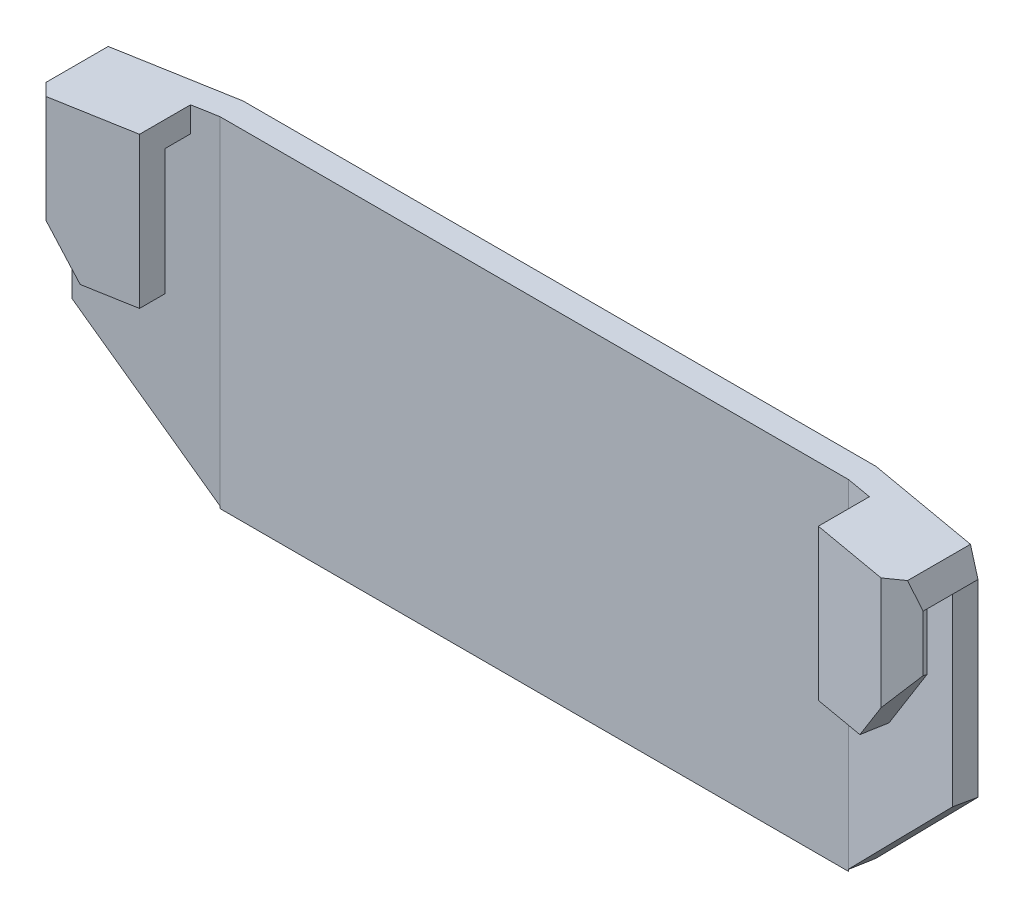
SolidWorks part; units mm, degrees
ref_plane "Front Plane" through (0, 0, 0) normal (0, 0, 1) x (1, 0, 0)
ref_plane "Top Plane" through (0, 0, 0) normal (0, 1, 0) x (1, 0, 0)
ref_plane "Right Plane" through (0, 0, 0) normal (1, 0, 0) x (0, 0, -1)
sketch "Sketch12" plane through (0, 0, 0) normal (0, 1, 0) x (1, 0, 0)
  line L24 (-27, -6.4144) -> (-27, -2.3527)
  line L25 (-27, -2.3527) -> (-25, -2)
  line L26 (35.0231, -1.7365) -> (25.175, 0)
  line L27 (25.175, 0) -> (-25.175, 0)
  line L28 (-25.175, 0) -> (-35.0231, -1.7365)
  line L29 (-25, -2) -> (25, -2)
  line L30 (35.0231, -7.829) -> (27, -6.4144)
  line L31 (27, -6.4144) -> (27, -2.3527)
  line L32 (-35.0231, -7.829) -> (-27, -6.4144)
  line L33 (-35.0231, -1.7365) -> (-35.0231, -7.829)
  line L34 (35.0231, -1.7365) -> (35.0231, -7.829)
  line L35 (27, -2.3527) -> (25, -2)
  point P12 (0, 0)
  dimension "D1" = 25
  dimension "D2" = 25.175
  dimension "D3" = 27
  dimension "D4" = 35.0231
  dimension "D5" = 1.7365
  dimension "D6" = 2
  dimension "D7" = 6.4144
extrude "Boss-Extrude1" add sketch "Sketch12" along normal blind 2
sketch "Sketch13" plane through (0, 0, 0) normal (0, -1, 0) x (1, 0, 0)
  line L0 (25.175, 0) -> (35.0231, 1.7365)
  line L1 (25.175, 0) -> (-25.175, 0)
  line L2 (-25.175, 0) -> (-35.0231, 1.7365)
  line L3 (25, 2) -> (27, 2.3527)
  line L5 (-25, 2) -> (25, 2)
  line L6 (27, 2.3527) -> (35.0231, 3.7673)
  line L7 (35.0231, 7.829) -> (35.0231, 1.7365) construction
  line L9 (35.0231, 3.7673) -> (35.0231, 1.7365)
  line L10 (-25, 2) -> (-27, 2.3527)
  line L11 (-27, 2.3527) -> (-35.0231, 3.7673)
  line L12 (-35.0231, 1.7365) -> (-35.0231, 7.829) construction
  line L13 (-35.0231, 3.7673) -> (-35.0231, 1.7365)
extrude "Boss-Extrude2" add sketch "Sketch13" along normal blind 25
sketch "Sketch14" plane through (0, 0, 0) normal (0, -1, 0) x (1, 0, 0)
  line L0 (-35.0231, 7.829) -> (-27, 6.4144)
  line L1 (-35.0231, 5.7982) -> (-27, 4.3835)
  line L2 (-35.0231, 3.7673) -> (-35.0231, 7.829) construction
  line L3 (-27, 6.4144) -> (-27, 2.3527) construction
  line L4 (-27, 4.3835) -> (-27, 6.4144)
  line L5 (-35.0231, 5.7982) -> (-35.0231, 7.829)
  line L7 (27, 6.4144) -> (35.0231, 7.829)
  line L8 (35.0231, 7.829) -> (35.0231, 5.7982)
  line L9 (35.0231, 7.829) -> (35.0231, 3.7673) construction
  line L10 (35.0231, 5.7982) -> (27, 4.3835)
  line L11 (27, 2.3527) -> (27, 6.4144) construction
  line L12 (27, 4.3835) -> (27, 6.4144)
  dimension "D1" = 2
  dimension "D2" = 2
extrude "Boss-Extrude3" add sketch "Sketch14" along normal blind 10
sketch "Sketch15" plane through (0.7591, 0, -4.3052) normal (0.1736, 0, -0.9848) x (-0.9848, 0, -0.1736)
  line L5 (-24.7925, -25) -> (-35.1452, -14.6473)
  line L6 (-35.1452, -25) -> (-35.1452, 0) construction
  line L7 (-35.1452, -14.6473) -> (-35.1452, -25)
  line L8 (-35.1452, -25) -> (-24.7925, -25)
  line L9 (24.7925, -25) -> (-24.7925, -25) construction
  dimension "D1" = 135
extrude "Cut-Extrude4" cut sketch "Sketch15" against normal up to surface (2 mm away) up to face at (29.0077, -7.6667, 2.7067)
sketch "Sketch16" plane through (-0.7591, 0, -4.3052) normal (-0.1736, 0, -0.9848) x (-0.9848, 0, 0.1736)
  line L5 (24.7925, -25) -> (35.1452, -14.6473)
  line L6 (35.1452, -25) -> (35.1452, 0) construction
  line L7 (35.1452, -14.6473) -> (35.1452, -25)
  line L8 (35.1452, -25) -> (24.7925, -25)
  line L9 (24.7925, -25) -> (-24.7925, -25) construction
  dimension "D1" = 135
extrude "Cut-Extrude5" cut sketch "Sketch16" against normal up to surface (2 mm away) up to face at (-29.0077, -7.6667, 2.7067)
sketch "Sketch18" plane through (0.2828, 0, 1.6037) normal (0.1736, 0, 0.9848) x (0.9848, 0, -0.1736)
  line L6 (-31.7771, -10) -> (-35.8505, -4)
  line L7 (-27.7037, -10) -> (-35.8505, -10) construction
  line L8 (-35.8505, 2) -> (-35.8505, -10) construction
  line L9 (-35.8505, -4) -> (-35.8505, -10)
  line L10 (-35.8505, -10) -> (-31.7771, -10)
extrude "Cut-Extrude6" cut sketch "Sketch18" against normal up to surface (2 mm away) up to face at (-31.0115, -5, 5.0908)
sketch "Sketch19" plane through (-0.2828, 0, 1.6037) normal (-0.1736, 0, 0.9848) x (0.9848, 0, 0.1736)
  line L6 (31.7771, -10) -> (35.8505, -4)
  line L7 (35.8505, -10) -> (27.7037, -10) construction
  line L8 (35.8505, 2) -> (35.8505, -10) construction
  line L9 (35.8505, -4) -> (35.8505, -10)
  line L10 (35.8505, -10) -> (31.7771, -10)
extrude "Cut-Extrude7" cut sketch "Sketch19" against normal up to surface (2 mm away) up to face at (31.0115, -5, 5.0908)
sketch "Sketch21" plane through (0, 2, 0) normal (0, 1, 0) x (1, 0, 0)
  line L1 (-25.175, 0) -> (-35.0231, -1.7365) construction
  line L2 (25.175, 0) -> (-25.175, 0) construction
  line L3 (-25.175, 0) -> (25.175, 0)
  line L6 (35.0231, -3.7673) -> (25, -2)
  line L7 (25, -2) -> (-25, -2)
  line L8 (-25, -2) -> (-27, -2.3527)
  line L9 (-27, -2.3527) -> (-35.0231, -3.7673)
  line L11 (-35.0231, -3.7673) -> (-35.0231, -1.7365)
  line L12 (-35.0231, -1.7365) -> (-25.175, 0)
  line L13 (35.0231, -1.7365) -> (25.175, 0)
  line L14 (35.0231, -1.7365) -> (35.0231, -3.7673)
extrude "Boss-Extrude4" [suppressed] add sketch "Sketch21" along normal blind 5
sketch "Sketch23" [suppressed] plane through (0, 0, 2) normal (0, 0, 1) x (1, 0, 0)
  line L2 (-25, 7) -> (-35.0231, 7)
  line L6 (35.0231, 7) -> (25, 7)
  line L8 (-35.0231, 7) -> (-35.0231, 2)
  line L9 (-35.0231, 2) -> (-25, 7)
  line L10 (35.0231, 7) -> (35.0231, 2)
  line L11 (35.0231, 2) -> (25, 7)
extrude "Cut-Extrude8" [suppressed] cut sketch "Sketch23" against normal up to surface and the other way up to vertex
chamfer "Chamfer1" distance 2 angle 20 2 edges at (-35.0231, 2, 4.7828) (35.0231, 2, 4.7828) first distance on face at (-35.0231, -4.2708, 4.7828) first distance on face at (35.0231, -4.2708, 4.7828)
chamfer "Chamfer2" distance 2 angle 45 2 edges at (-35.0231, -2, 7.829) (35.0231, -2, 7.829) first distance on face at (-35.0231, -2.1299, 6.8136) first distance on face at (31.5588, -3.3333, 7.2182)
